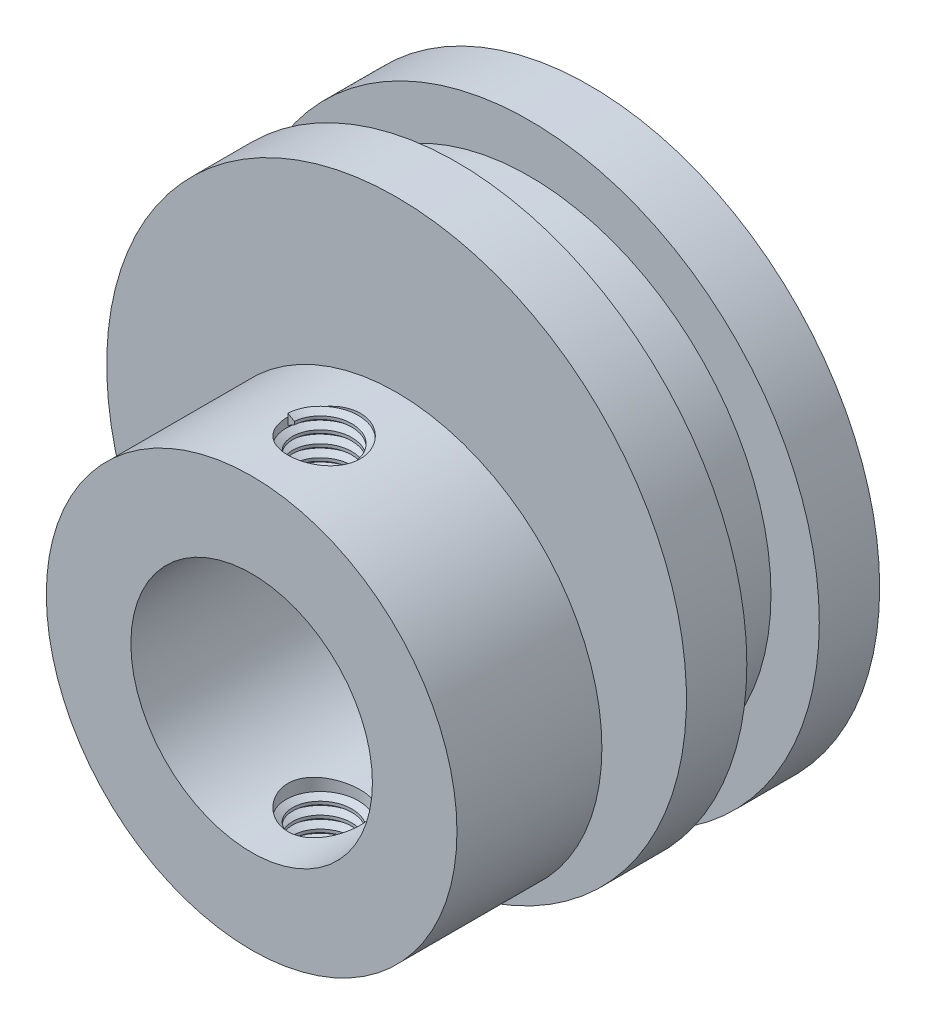
SolidWorks part; units mm, degrees
ref_plane "Front Plane" through (0, 0, 0) normal (0, 0, 1) x (1, 0, 0)
ref_plane "Top Plane" through (0, 0, 0) normal (0, 1, 0) x (1, 0, 0)
ref_plane "Right Plane" through (0, 0, 0) normal (1, 0, 0) x (0, 0, -1)
sketch "Sketch1" plane through (0, 0, 0) normal (0, 0, 1) x (1, 0, 0)
  circle A0 centre (0, 0) radius 12
  dimension "D1" = 24
extrude "Boss-Extrude1" add sketch "Sketch1" along normal blind 2.5
sketch "Sketch2" plane through (0, 0, 2.5) normal (0, 0, 1) x (1, 0, 0)
  circle A0 centre (0, 0) radius 10
  dimension "D1" = 20
extrude "Boss-Extrude2" add sketch "Sketch2" along normal blind 3
sketch "Sketch3" plane through (0, 0, 5.5) normal (0, 0, 1) x (1, 0, 0)
  circle A0 centre (0, 0) radius 12
extrude "Boss-Extrude3" add sketch "Sketch3" along normal blind 2.5
sketch "Sketch4" plane through (0, 0, 8) normal (0, 0, 1) x (1, 0, 0)
  circle A0 centre (0, -3.5) radius 8.5
  dimension "D1" = 3.5
  dimension "D2" = 17
extrude "Boss-Extrude4" add sketch "Sketch4" along normal blind 6
sketch "Sketch5" plane through (0, 0, 14) normal (0, 0, 1) x (1, 0, 0)
  circle A0 centre (0, -3.5) radius 5
  dimension "D1" = 10
extrude "Cut-Extrude1" cut sketch "Sketch5" against normal through all
sketch "Sketch6" plane through (0, 0, 0) normal (0, 1, 0) x (1, 0, 0)
  line L0 (-8.5, -14) -> (8.5, -14) construction
  circle A0 centre (0, -11) radius 1.5
  point P2 (0, 0)
  dimension "D1" = 3
  dimension "D2" = 3
extrude "Cut-Extrude2" cut sketch "Sketch6" against normal mid plane 28
ref_plane "Plane2" through (0, 5, 0) normal (0, 1, 0) x (1, 0, 0)
thread "Thread1" pitch 0.5 method extrude profile "Thread Profile2" start angle 0, offset 0, length 3, pitch 0.5, diameter 3
ref_plane "Plane3" through (-1.5, 5, 11) normal (0, 0, 1) x (-1, 0, 0)
sketch "Thread Profile2" plane through (-1.5, 5, 11) normal (0, 0, 1) x (-1, 0, 0)
  line L0 (0, 0) -> (0, 0.5) construction
  line L11 (0, 0) -> (0, 0.4375)
  line L12 (0, 0.4375) -> (-0.2706, 0.2812)
  line L13 (-0.2706, 0.2812) -> (-0.2706, 0.1562)
  line L15 (-0.2706, 0.1562) -> (0, 0)
  line L17 (-0.2706, 0.2187) -> (0, 0.2187) construction
  point P2 (0, 0)
  dimension "Pitch" = 0.5
  dimension "Profile_Angle" = 60
  dimension "Profile_Land" = 0.125
  dimension "Profile_Height" = 0.2706
ref_plane "Plane4" through (0, -12, 0) normal (0, 1, 0) x (1, 0, 0)
thread "Thread2" pitch 0.5 method extrude profile "Thread Profile3" start angle 0, offset 0, length 3, pitch 0.5, diameter 3
ref_plane "Plane5" through (1.5, -12, 11) normal (0, 0, 1) x (1, 0, 0)
sketch "Thread Profile3" plane through (1.5, -12, 11) normal (0, 0, 1) x (1, 0, 0)
  line L0 (0, 0) -> (0, 0.5) construction
  line L11 (0, 0) -> (0, 0.4375)
  line L12 (0, 0.4375) -> (-0.2706, 0.2812)
  line L13 (-0.2706, 0.2812) -> (-0.2706, 0.1562)
  line L15 (-0.2706, 0.1562) -> (0, 0)
  line L17 (-0.2706, 0.2187) -> (0, 0.2187) construction
  point P2 (0, 0)
  dimension "Pitch" = 0.5
  dimension "Profile_Angle" = 60
  dimension "Profile_Land" = 0.125
  dimension "Profile_Height" = 0.2706
